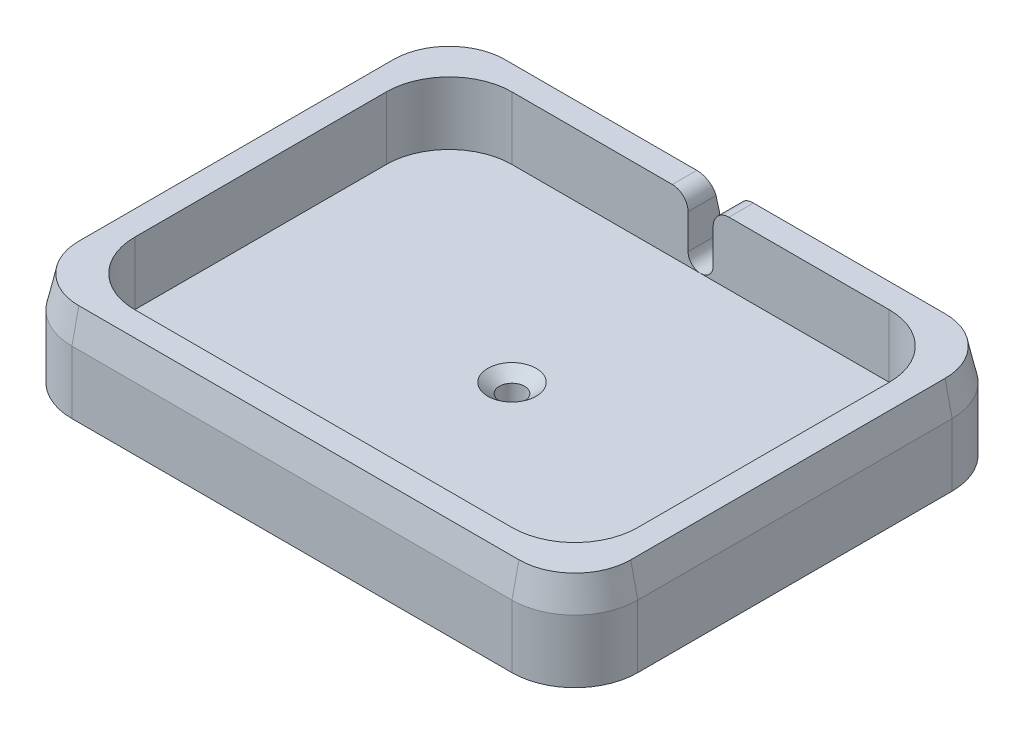
SolidWorks part; units mm, degrees
ref_plane "Front Plane" through (0, 0, 0) normal (0, 0, 1) x (1, 0, 0)
ref_plane "Top Plane" through (0, 0, 0) normal (0, 1, 0) x (1, 0, 0)
ref_plane "Right Plane" through (0, 0, 0) normal (1, 0, 0) x (0, 0, -1)
sketch "Sketch1" plane through (0, 0, 0) normal (0, 1, 0) x (1, 0, 0)
  line L0 (-57.15, -44.45) -> (-57.15, 44.45)
  line L1 (-50.8, -38.1) -> (50.8, -38.1)
  line L2 (-50.8, -38.1) -> (-50.8, 38.1)
  line L3 (-50.8, 38.1) -> (50.8, 38.1)
  line L4 (50.8, -38.1) -> (50.8, 38.1)
  line L5 (-50.8, -38.1) -> (50.8, 38.1) construction
  line L6 (-50.8, 38.1) -> (50.8, -38.1) construction
  line L7 (-57.15, 44.45) -> (57.15, 44.45)
  line L8 (57.15, -44.45) -> (57.15, 44.45)
  line L9 (-57.15, -44.45) -> (57.15, -44.45)
  point P0 (0, 0)
  dimension "D1" = 101.6
  dimension "D2" = 76.2
  dimension "D3" = 6.35
extrude "Boss-Extrude1" add sketch "Sketch1" along normal blind 12.7
sketch "Sketch2" plane through (0, 0, 0) normal (0, -1, 0) x (1, 0, 0)
  line L1 (-57.15, 44.45) -> (57.15, 44.45)
  line L2 (-57.15, 44.45) -> (-57.15, -44.45)
  line L3 (-57.15, -44.45) -> (57.15, -44.45)
  line L4 (57.15, 44.45) -> (57.15, -44.45)
extrude "Boss-Extrude2" add sketch "Sketch2" along normal blind 6.35
fillet "Fillet1" radius 12.7 8 edges at (57.15, 3.175, 44.45) (-57.15, 3.175, 44.45) (-57.15, 3.175, -44.45) (57.15, 3.175, -44.45) (-50.8, 6.35, -38.1) (-50.8, 6.35, 38.1) (50.8, 6.35, 38.1) (50.8, 6.35, -38.1)
sketch "Sketch3" plane through (0, 0, -44.45) normal (0, 0, -1) x (-1, 0, 0)
  line L0 (0, 22.86) -> (0, 2.54) construction
  line L1 (-44.45, 12.7) -> (44.45, 12.7) construction
  line L2 (2.54, 22.86) -> (2.54, 2.54)
  line L3 (-2.54, 22.86) -> (-2.54, 2.54)
  arc A0 (2.54, 22.86) -> (-2.54, 22.86) centre (0, 22.86) ccw
  arc A1 (-2.54, 2.54) -> (2.54, 2.54) centre (0, 2.54) ccw
  point P5 (0, 12.7)
  point P10 (0, 0)
  dimension "D1" = 5.08
extrude "Cut-Extrude1" cut sketch "Sketch3" against normal up to next
fillet "Fillet2" radius 3.175 2 edges at (-2.54, 12.7, -41.275) (2.54, 12.7, -41.275)
hole_wizard "CSK for #10 Flat Head Machine Screw (100)1" positions "Sketch5" profile "Sketch4" countersink size "#10" standard "ANSI Inch" end condition through all
sketch "Sketch5" plane through (0, 0, 0) normal (0, 1, 0) x (1, 0, 0)
  point P0 (0, 0)
sketch "Sketch4" plane through (0, 0, 0) normal (1, 0, 0) x (0, 0, 1)
  line L0 (0, 0) -> (0, 6.35)
  line L1 (0, 6.35) -> (2.5527, 6.35)
  line L2 (2.5527, 6.35) -> (2.5527, 1.9608)
  line L3 (2.5527, 1.9608) -> (4.8895, 0)
  line L5 (4.8895, 0) -> (0, 0)
  line L6 (-2.5527, 1.9608) -> (-4.8895, 0) construction
  line L11 (0, -6.35) -> (0, 107.95) construction
  dimension "Thru Hole Dia." = 5.1054
  dimension "Thru Hole Depth" = 6.35
  dimension "Near C'Sink Dia." = 9.779
  dimension "Near C'Sink Angle" = 100
chamfer "Chamfer1" distance 6.35 angle 12.5 8 edges at (-53.4303, 12.7, -40.7303) (-25.0825, 12.7, -44.45) (25.0825, 12.7, -44.45) (-53.4303, 12.7, 40.7303) (0, 12.7, 44.45) (53.4303, 12.7, 40.7303) (53.4303, 12.7, -40.7303) (57.15, 12.7, 0)
